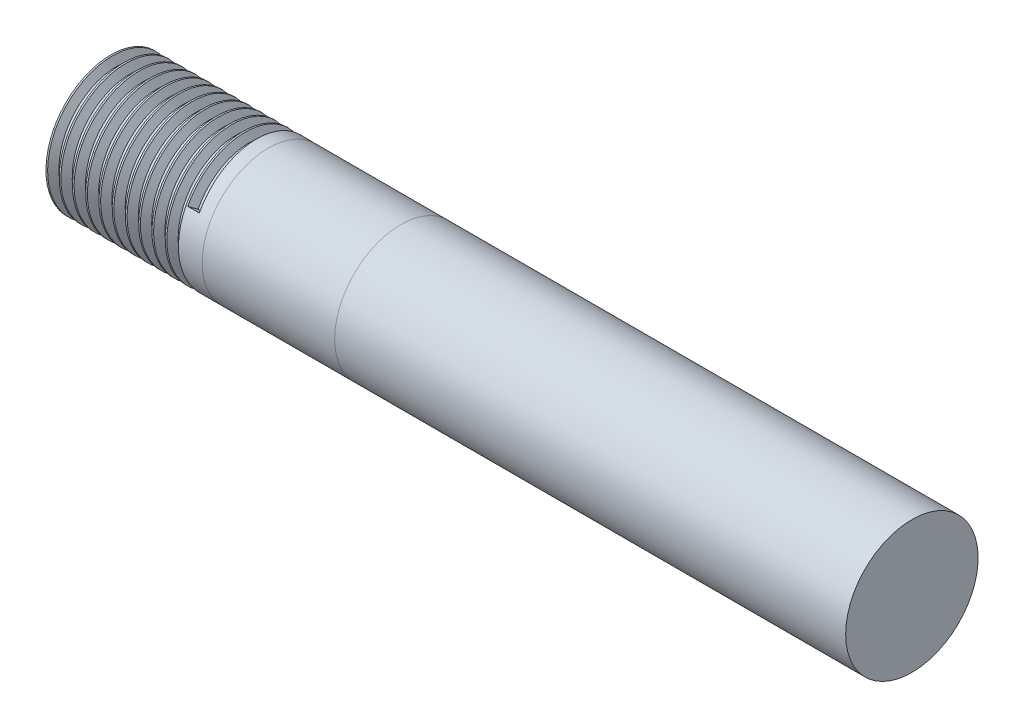
SolidWorks part; units mm, degrees
ref_plane "Front Plane" through (0, 0, 0) normal (0, 0, 1) x (1, 0, 0)
ref_plane "Top Plane" through (0, 0, 0) normal (0, 1, 0) x (1, 0, 0)
ref_plane "Right Plane" through (0, 0, 0) normal (1, 0, 0) x (0, 0, -1)
sketch "Sketch1" plane through (0, 0, 0) normal (0, 0, 1) x (1, 0, 0)
  line L0 (0, 0) -> (0, 6.35)
  line L1 (0, 6.35) -> (77.1507, 6.35)
  line L4 (77.1507, 6.35) -> (77.1507, 0)
  line L5 (77.1507, 0) -> (0, 0)
  line L6 (-315.9627, 0) -> (15482.1706, 0) construction
  dimension "D1" = 12.7
  dimension "D3" = 77.1507
revolve "Revolve1" add sketch "Sketch1" angle 360 about L6
thread "Thread1" pitch 1.27 method cut profile "Thread Profile1" start angle 0, offset 1.27, length 14.5, pitch 1.27, diameter 12.7
ref_plane "Plane1" through (-1.27, 0, -6.35) normal (0, -1, 0) x (0, 0, -1)
sketch "Thread Profile1" plane through (-1.27, 0, -6.35) normal (0, -1, 0) x (0, 0, -1)
  line L0 (0, 0) -> (0, 1.27) construction
  line L11 (0, 0) -> (0, 1.1112)
  line L12 (0, 1.1112) -> (-0.6874, 0.7144)
  line L13 (-0.6874, 0.7144) -> (-0.6874, 0.3969)
  line L15 (-0.6874, 0.3969) -> (0, 0)
  line L17 (-0.6874, 0.5556) -> (0, 0.5556) construction
  point P2 (0, 0)
  dimension "Pitch" = 1.27
  dimension "Profile_Angle" = 60
  dimension "Profile_Land" = 0.3175
  dimension "Profile_Height" = 0.6874
sketch "Sketch2" plane through (0, 0, 0) normal (0, 0, 1) x (1, 0, 0)
  line L0 (28.1507, 6.35) -> (28.1507, -6.35)
  line L1 (77.1507, 6.35) -> (14.1287, 6.35) construction
  line L2 (13.4937, -6.35) -> (77.1507, -6.35) construction
  line L3 (15.4507, 6.35) -> (15.4507, -6.35)
  line L4 (-3.5993, 6.35) -> (-3.5993, -6.35)
  line L5 (-16.2993, 6.35) -> (-16.2993, -6.35)
  line L6 (77.1507, -6.35) -> (77.1507, 6.35) construction
  dimension "D1" = 49
  dimension "D2" = 12.7
  dimension "D3" = 12.7
  dimension "D4" = 19.05
split line "Split Line1"
